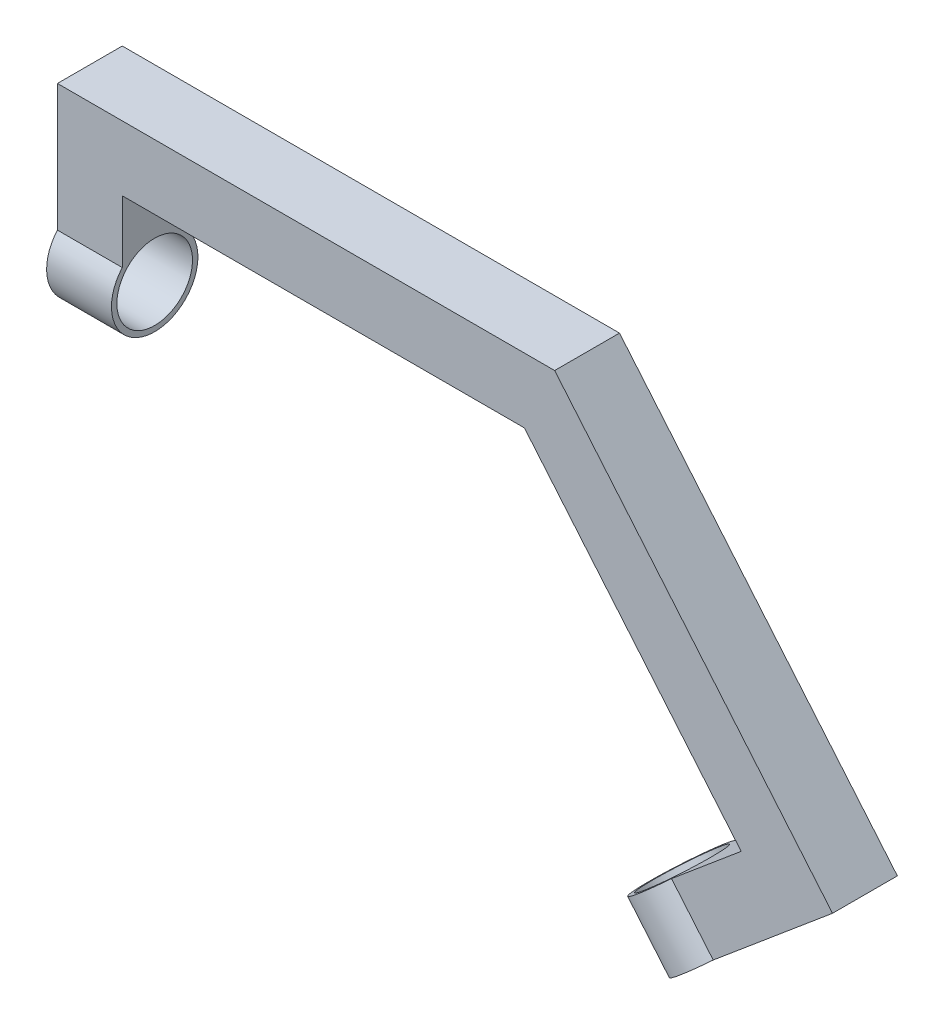
SolidWorks part; units mm, degrees
ref_plane "Front Plane" through (0, 0, 0) normal (0, 0, 1) x (1, 0, 0)
ref_plane "Top Plane" through (0, 0, 0) normal (0, 1, 0) x (1, 0, 0)
ref_plane "Right Plane" through (0, 0, 0) normal (1, 0, 0) x (0, 0, -1)
sketch "Sketch1" plane through (0, 0, 0) normal (0, 0, 1) x (1, 0, 0)
  line L0 (14.6198, 5.9454) -> (41.5141, 28.5124)
  line L1 (41.5141, 28.5124) -> (-22.1649, 104.402)
  line L3 (26.8649, -8.6478) -> (68.3523, 26.1643)
  line L4 (68.3523, 26.1643) -> (-13.2817, 123.452)
  line L5 (-140.3137, 77.732) -> (-140.3137, 104.402)
  line L6 (-140.3137, 77.732) -> (-159.3637, 77.732)
  line L7 (-159.3637, 77.732) -> (-159.3637, 123.452)
  line L8 (-159.3637, 123.452) -> (-13.2817, 123.452)
  line L9 (-140.3137, 104.402) -> (-22.1649, 104.402)
  line L10 (41.5141, 28.5124) -> (-114.0043, 28.5124) construction
  line L11 (26.8649, -8.6478) -> (68.3523, 26.1643) construction
  line L12 (26.8649, -8.6478) -> (14.6198, 5.9454)
  dimension "D1" = 146.082
  dimension "D2" = 50
  dimension "D3" = 19.05
  dimension "D4" = 19.05
  dimension "D5" = 19.05
  dimension "D6" = 19.05
  dimension "D7" = 45.72
  dimension "D8" = 127
  dimension "D9" = 54.158
extrude "Boss-Extrude1" add sketch "Sketch1" along normal blind 9.525 and the other way blind 9.525
sketch "Sketch2" plane through (-159.3637, 0, 0) normal (-1, 0, 0) x (0, 0, 1)
  line L0 (-9.525, 77.732) -> (9.525, 77.732) construction
  circle A0 centre (0, 77.732) radius 12.7
  dimension "D1" = 25.4
extrude "Boss-Extrude2" add sketch "Sketch2" against normal blind 19.05
sketch "Sketch3" plane through (15.3581, -18.3031, 0) normal (0.6428, -0.766, 0) x (0.766, 0.6428, 0)
  line L1 (15.021, 9.525) -> (15.021, 0) construction
  line L2 (15.021, -9.525) -> (15.021, 9.525) construction
  circle A0 centre (15.021, 0) radius 12.7
extrude "Boss-Extrude3" add sketch "Sketch3" against normal blind 19.05
sketch "Sketch4" plane through (15.3581, -18.3031, 0) normal (0.6428, -0.766, 0) x (0.766, 0.6428, 0)
  circle A0 centre (15.021, 0) radius 11.1125
  dimension "D1" = 22.225
extrude "Cut-Extrude1" cut sketch "Sketch4" against normal blind 19.05
sketch "Sketch5" plane through (-159.3637, 0, 0) normal (-1, 0, 0) x (0, 0, 1)
  circle A0 centre (0, 77.732) radius 11.1125
  dimension "D1" = 22.225
extrude "Cut-Extrude2" cut sketch "Sketch5" against normal blind 19.05
equation "\"bushing outer diameter\"= 0.875"
equation "\"D1@Sketch2\"=\"bushing outer diameter\" + (1/8)"
equation "\"D1@Sketch5\"=\"bushing outer diameter\""
equation "\"D1@Sketch4\"=\"bushing outer diameter\""
equation "\"Column Angle\"= 50"
equation "\"D2@Sketch1\"=\"Column Angle\""
